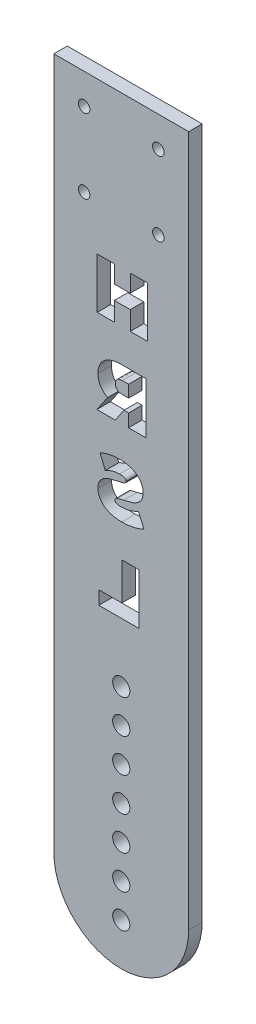
SolidWorks part; units mm, degrees
other "Markup1"
sketch "Sketch7" plane through (-20, 225, -2) normal (-0.1146, 0.1086, -0.9875) x (-0.991, 0.0573, 0.1213)
sketch "Sketch10" plane through (-20, 225, -2) normal (-0.1146, 0.1086, -0.9875) x (-0.991, 0.0573, 0.1213)
ref_plane "Front Plane" through (0, 0, 0) normal (0, 0, 1) x (1, 0, 0)
ref_plane "Top Plane" through (0, 0, 0) normal (0, 1, 0) x (1, 0, 0)
ref_plane "Right Plane" through (0, 0, 0) normal (1, 0, 0) x (0, 0, -1)
sketch "Sketch1" plane through (0, 0, 0) normal (0, 1, 0) x (1, 0, 0)
  line L1 (-20, 2) -> (20, 2)
  line L2 (-20, 2) -> (-20, -2)
  line L3 (-20, -2) -> (20, -2)
  line L4 (20, 2) -> (20, -2)
  line L5 (-20, 2) -> (20, -2) construction
  line L6 (-20, -2) -> (20, 2) construction
  point P0 (0, 0)
extrude "Boss-Extrude1" add sketch "Sketch1" along normal blind 225
fillet "Fillet1" radius 20 2 edges at (-20, 0, 0) (20, 0, 0)
sketch "Sketch2" plane through (0, 0, 2) normal (0, 0, 1) x (1, 0, 0)
  circle A0 centre (0, 12.5) radius 2.55
  dimension "D1" = 12.5
extrude "Cut-Extrude1" cut sketch "Sketch2" against normal through all
pattern_linear "LPattern1" count 7 spacing 10 along (0, 1, 0) of "Cut-Extrude1"
sketch "Sketch8" plane through (0, 0, -2) normal (0, 0, -1) x (-1, 0, 0)
  line L0 (-20, 225) -> (20, 225) construction
  line L1 (-20, 225) -> (-20, 20) construction
  line L2 (20, 225) -> (20, 20) construction
  line L3 (-20, 185) -> (20, 185) construction
  circle A0 centre (-11, 216) radius 1.7
  circle A1 centre (11, 216) radius 1.7
  circle A2 centre (-11, 194) radius 1.7
  circle A3 centre (11, 194) radius 1.7
  dimension "D1" = 9
  dimension "D3" = 9
  dimension "D5" = 3.4
  dimension "D2" = 9
  dimension "D4" = 9
  dimension "D6" = 40
  dimension "D7" = 9
extrude "Cut-Extrude4" cut sketch "Sketch8" against normal through all
sketch "Sketch9" plane through (0, 0, -2) normal (0, 0, -1) x (-1, 0, 0)
  line L0 (0, 182.004) -> (0, 90.0353) construction
  text T0 "<b><r0>H</r></b>" font "@Adobe Fan Heiti Std B" height 15
  text T1 "<b>R</b>" font "@Adobe Fan Heiti Std B" height 15
  text T2 "<b>S</b>" font "@Adobe Fan Heiti Std B" height 15
  text T3 "<b>L</b>" font "@Adobe Fan Heiti Std B" height 15
  point P7 (0, 140.0353)
  point P8 (0, 165.0353)
  point P9 (0, 115.0353)
  dimension "D1" = 25
  dimension "D2" = 25
  dimension "D3" = 25
  dimension "D4" = 9
  dimension "D5" = 8.5
  dimension "D6" = 7
  dimension "D7" = 6.5
extrude "Cut-Extrude5" cut sketch "Sketch9" against normal through all
